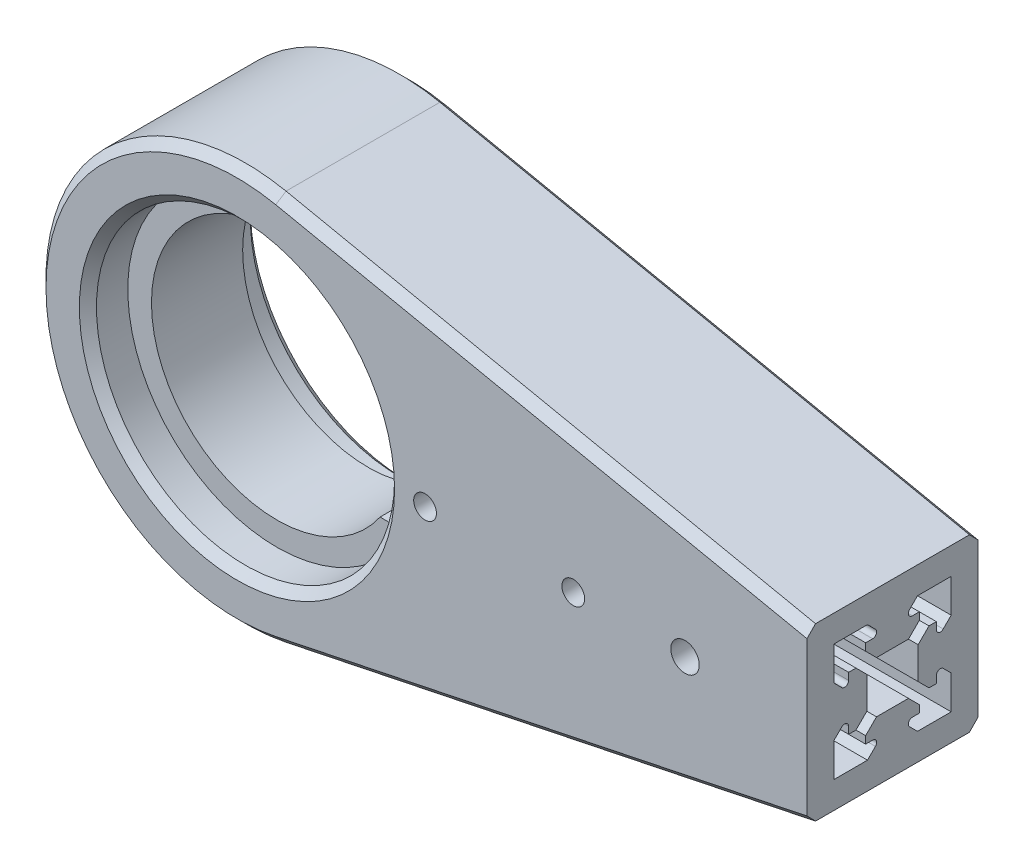
SolidWorks part; units mm, degrees
ref_plane "Front Plane" through (0, 0, 0) normal (0, 0, 1) x (1, 0, 0)
ref_plane "Top Plane" through (0, 0, 0) normal (0, 1, 0) x (1, 0, 0)
ref_plane "Right Plane" through (0, 0, 0) normal (1, 0, 0) x (0, 0, -1)
sketch "Sketch1" plane through (0, 0, 0) normal (0, 0, 1) x (1, 0, 0)
  line L0 (100, 15) -> (100, -15)
  line L1 (7.1095, 34.2703) -> (100, 15)
  line L2 (100, -15) -> (7.1095, -34.2703)
  circle A0 centre (0, 0) radius 26.15
  arc A1 (7.1095, 34.2703) -> (7.1095, -34.2703) centre (0, 0) ccw
  circle A2 centre (59, 0) radius 2
  circle A3 centre (78.6, 0) radius 2.5
  circle A4 centre (33, 0) radius 2
  point P6 (100, 0)
  dimension "D1" = 52.3
  dimension "D2" = 70
  dimension "D8" = 4
  dimension "D9" = 5
  dimension "D3" = 30
  dimension "D4" = 100
  dimension "D5" = 21.4
  dimension "D6" = 19.6
  dimension "D7" = 26
extrude "Boss-Extrude1" add sketch "Sketch1" along normal blind 30
sketch "Sketch2" plane through (0, 0, 30) normal (0, 0, 1) x (1, 0, 0)
  line L1 (18.1039, 12.5) -> (22.9689, 12.5)
  line L3 (18.1039, -12.5) -> (22.9689, -12.5)
  circle A0 centre (0, 0) radius 26.15 construction
  arc A1 (22.9689, 12.5) -> (22.9689, -12.5) centre (0, 0) ccw
  arc A2 (18.1039, 12.5) -> (18.1039, -12.5) centre (0, 0) ccw
  dimension "D1" = 44
  dimension "D2" = 25
extrude "Boss-Extrude2" add sketch "Sketch2" against normal blind 16 from offset 7 offset against normal yes
chamfer "Chamfer1" distance 1.5 angle 45 8 edges at (26.15, 0, 30) (26.15, 0, 0) (53.5547, 24.6352, 30) (-35, 0, 30) (53.5547, -24.6352, 30) (53.5547, 24.6352, 0) (-35, 0, 0) (53.5547, -24.6352, 0)
sketch "Sketch3" plane through (100, 0, 0) normal (1, 0, 0) x (0, 0, -1)
  line L0 (-12.1971, 4.5) -> (-17.8029, 4.5)
  line L1 (-17.8029, 4.5) -> (-19.7101, 6.4071)
  line L2 (-19.7101, 6.4071) -> (-19.7101, 7.7)
  line L3 (-19.7101, 7.7) -> (-18.4828, 7.7)
  line L4 (-17.9879, 8.895) -> (-19.3879, 10.295)
  line L5 (-25.295, 4.3879) -> (-23.895, 2.9879)
  line L6 (-22.7, 3.4828) -> (-22.7, 4.7101)
  line L7 (-22.7, 4.7101) -> (-21.4071, 4.7101)
  line L8 (-21.4071, 4.7101) -> (-19.5, 2.8029)
  line L9 (-19.5, 2.8029) -> (-19.5, -2.8029)
  line L10 (-19.5, -2.8029) -> (-21.4071, -4.7101)
  line L11 (-21.4071, -4.7101) -> (-22.7, -4.7101)
  line L12 (-22.7, -4.7101) -> (-22.7, -3.4828)
  line L13 (-23.895, -2.9879) -> (-25.295, -4.3879)
  line L14 (-19.3879, -10.295) -> (-17.9879, -8.895)
  line L15 (-18.4828, -7.7) -> (-19.7101, -7.7)
  line L16 (-19.7101, -7.7) -> (-19.7101, -6.4071)
  line L17 (-19.7101, -6.4071) -> (-17.8029, -4.5)
  line L18 (-17.8029, -4.5) -> (-12.1971, -4.5)
  line L19 (-19.3879, -10.295) -> (-25.295, -10.295)
  line L20 (-25.295, -10.295) -> (-25.295, -4.3879)
  line L21 (-25.295, 4.3879) -> (-25.295, 10.295)
  line L22 (-25.295, 10.295) -> (-19.3879, 10.295)
  line L23 (-15, 15.274) -> (-15, -14.726) construction
  line L24 (-4.705, 10.295) -> (-10.6121, 10.295)
  line L25 (-4.705, 4.3879) -> (-4.705, 10.295)
  line L26 (-4.705, -10.295) -> (-4.705, -4.3879)
  line L27 (-10.6121, -10.295) -> (-4.705, -10.295)
  line L28 (-10.2899, -6.4071) -> (-12.1971, -4.5)
  line L29 (-10.2899, -7.7) -> (-10.2899, -6.4071)
  line L30 (-11.5172, -7.7) -> (-10.2899, -7.7)
  line L31 (-10.6121, -10.295) -> (-12.0121, -8.895)
  line L32 (-6.105, -2.9879) -> (-4.705, -4.3879)
  line L33 (-7.3, -4.7101) -> (-7.3, -3.4828)
  line L34 (-8.5929, -4.7101) -> (-7.3, -4.7101)
  line L35 (-10.5, -2.8029) -> (-8.5929, -4.7101)
  line L36 (-10.5, 2.8029) -> (-10.5, -2.8029)
  line L37 (-8.5929, 4.7101) -> (-10.5, 2.8029)
  line L38 (-7.3, 4.7101) -> (-8.5929, 4.7101)
  line L39 (-7.3, 3.4828) -> (-7.3, 4.7101)
  line L40 (-4.705, 4.3879) -> (-6.105, 2.9879)
  line L41 (-12.0121, 8.895) -> (-10.6121, 10.295)
  line L42 (-10.2899, 7.7) -> (-11.5172, 7.7)
  line L43 (-10.2899, 6.4071) -> (-10.2899, 7.7)
  line L44 (-12.1971, 4.5) -> (-10.2899, 6.4071)
  line L45 (-28.5, 15) -> (-1.5, 15) construction
  arc A0 (-12.0121, -8.895) -> (-11.5172, -7.7) centre (-11.5172, -8.4) cw
  arc A1 (-18.4828, 7.7) -> (-17.9879, 8.895) centre (-18.4828, 8.4) ccw
  arc A2 (-7.3, -3.4828) -> (-6.105, -2.9879) centre (-6.6, -3.4828) cw
  arc A3 (-6.105, 2.9879) -> (-7.3, 3.4828) centre (-6.6, 3.4828) cw
  arc A4 (-23.895, 2.9879) -> (-22.7, 3.4828) centre (-23.4, 3.4828) ccw
  arc A5 (-22.7, -3.4828) -> (-23.895, -2.9879) centre (-23.4, -3.4828) ccw
  arc A6 (-11.5172, 7.7) -> (-12.0121, 8.895) centre (-11.5172, 8.4) cw
  arc A7 (-17.9879, -8.895) -> (-18.4828, -7.7) centre (-18.4828, -8.4) ccw
  point P0 (-15, 4.5)
  point P64 (-10.5, 0)
  point P68 (-15, 15)
  dimension "D7" = 0.7
  dimension "D16" = 0.7
  dimension "D31" = 0.7
  dimension "D1" = 5.6059
  dimension "D2" = 2.6971
  dimension "D3" = 1.2929
  dimension "D4" = 2.595
  dimension "D5" = 135
  dimension "D6" = 1.2934
  dimension "D8" = 1.9799
  dimension "D9" = 135
  dimension "D10" = 1.2272
  dimension "D11" = 5.6059
  dimension "D12" = 2.6971
  dimension "D13" = 1.2929
  dimension "D14" = 1.2272
  dimension "D15" = 1.2934
  dimension "D17" = 1.9799
  dimension "D18" = 225
  dimension "D19" = 5.9071
  dimension "D20" = 135
  dimension "D21" = 90
  dimension "D22" = 135
  dimension "D23" = 2.595
  dimension "D24" = 135
  dimension "D25" = 135
  dimension "D26" = 1.2934
  dimension "D27" = 5.9071
  dimension "D28" = 1.9799
  dimension "D29" = 135
  dimension "D30" = 1.2934
  dimension "D32" = 1.2272
  dimension "D33" = 90
  dimension "D34" = 135
  dimension "D35" = 1.2929
  dimension "D36" = 2.595
  dimension "D37" = 2.6971
  dimension "D38" = 5.6059
  dimension "D39" = 5.9071
extrude "Cut-Extrude1" cut sketch "Sketch3" against normal blind 90
